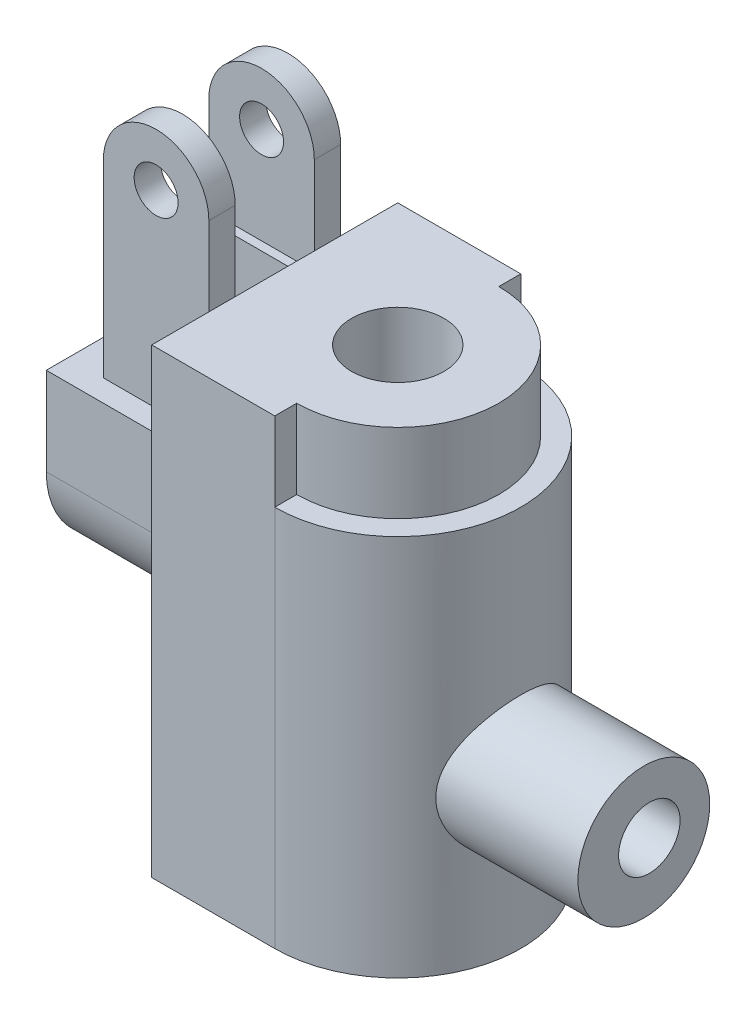
SolidWorks part; units mm, degrees
ref_plane "前视基准面" through (0, 0, 0) normal (0, 0, 1) x (1, 0, 0)
ref_plane "上视基准面" through (0, 0, 0) normal (0, 1, 0) x (1, 0, 0)
ref_plane "右视基准面" through (0, 0, 0) normal (1, 0, 0) x (0, 0, -1)
sketch "草图1" plane through (0, 0, 0) normal (0, 1, 0) x (1, 0, 0)
  line L1 (-14, 28) -> (14, 28)
  line L2 (-14, 28) -> (-14, -28)
  line L3 (-14, -28) -> (14, -28)
  line L5 (-14, 28) -> (14, -28) construction
  line L6 (-14, -28) -> (14, 28) construction
  arc A1 (14, -28) -> (14, 28) centre (14, 0) ccw
  point P0 (0, 0)
  dimension "D3" = 28
  dimension "D1" = 56
  dimension "D2" = 28
extrude "凸台-拉伸1" add sketch "草图1" along normal blind 105
sketch "草图2" plane through (-14, 0, 0) normal (-1, 0, 0) x (0, 0, 1)
  line L0 (0, 70) -> (0, 0) construction
  line L1 (-20, 80) -> (20, 80)
  line L2 (-20, 80) -> (-20, 60)
  line L3 (-20, 60) -> (20, 60)
  line L4 (20, 80) -> (20, 60)
  line L5 (-20, 80) -> (20, 60) construction
  line L6 (-20, 60) -> (20, 80) construction
  arc A0 (20, 60) -> (-20, 60) centre (0, 60) cw
  point P0 (0, 70)
  dimension "D3" = 70
  dimension "D1" = 20
  dimension "D2" = 40
extrude "凸台-拉伸2" add sketch "草图2" along normal blind 32 contours A0 L3 | L4 L1 L2 L3 region at (-14, 70, 0) region at (-14, 51.5117, 0)
ref_plane "基准面1" through (42, 0, 0) normal (1, 0, 0) x (0, 0, -1)
sketch "草图3" plane through (42, 0, 0) normal (1, 0, 0) x (0, 0, -1)
  line L0 (-28, 0) -> (28, 0) construction
  line L1 (0, 35) -> (0, -0.708) construction
  circle A0 centre (0, 35) radius 15
  dimension "D1" = 30
  dimension "D2" = 35
extrude "凸台-拉伸4" add sketch "草图3" against normal up to surface (4.3568 mm away) contours A0 up to face at (28, 52.5, 0)
sketch "草图4" plane through (42, 0, 0) normal (1, 0, 0) x (0, 0, -1)
  arc A2 (0, 50) -> (0, 20) centre (0, 35) ccw
  arc A3 (0, 20) -> (0, 50) centre (0, 35) ccw
  arc A4 (0, 50) -> (0, 20) centre (0, 35) ccw
  arc A5 (0, 20) -> (0, 50) centre (0, 35) ccw
  dimension "D1" = 0
extrude "凸台-拉伸5" add sketch "草图4" along normal offset from surface (28 mm away) 116 up to face at (-46, 65, 0)
sketch "草图5" plane through (0, 0, 0) normal (0, 0, 1) x (1, 0, 0)
  line L0 (-14, 0) -> (14, 0) construction
  line L1 (-38, 123) -> (-14, 123)
  line L2 (-38, 123) -> (-38, 80)
  line L3 (-38, 80) -> (-14, 80)
  line L4 (-14, 123) -> (-14, 80)
  line L5 (-38, 123) -> (-14, 80) construction
  line L6 (-38, 80) -> (-14, 123) construction
  arc A0 (-14, 123) -> (-38, 123) centre (-26, 123) ccw
  point P0 (-26, 101.5)
  dimension "D1" = 24
  dimension "D2" = 123
extrude "凸台-拉伸6" add sketch "草图5" along normal blind 8 from offset 7 contours L4 L1 L2 L3 | L1 A0 region at (-26, 128.093, 0) region at (-26, 101.5, 0)
mirror "镜向1" about plane through (0, 0, 0) normal (0, 0, 1) of "凸台-拉伸6"
sketch "草图6" plane through (0, 0, 0) normal (0, 0, 1) x (1, 0, 0)
  line L0 (-26, 126) -> (-26, 80) construction
  line L1 (-38, 151) -> (-14, 151)
  line L2 (-38, 151) -> (-38, 101)
  line L3 (-38, 101) -> (-14, 101)
  line L4 (-14, 151) -> (-14, 101)
  line L5 (-38, 151) -> (-14, 101) construction
  line L6 (-38, 101) -> (-14, 151) construction
  line L7 (-38, 80) -> (-14, 80) construction
  line L8 (-46, 80) -> (-14, 80) construction
  line L9 (-38, 123) -> (-38, 80) construction
  point P0 (-26, 126)
  point P11 (-9.3633, 126)
  dimension "D1" = 50
  dimension "D2" = 21
extrude "切除-拉伸1" cut sketch "草图6" against normal mid plane 18
sketch "草图7" plane through (0, 0, 15) normal (0, 0, 1) x (1, 0, 0)
  circle A0 centre (-26, 123) radius 5
  arc A1 (-14, 123) -> (-38, 123) centre (-26, 123) ccw construction
  dimension "D1" = 10
extrude "切除-拉伸2" cut sketch "草图7" against normal through all both and the other way through all
sketch "草图8" plane through (0, 0, 0) normal (0, 0, 1) x (1, 0, 0)
  line L0 (-14, 5) -> (-43.3685, 40)
  line L1 (-14, 105) -> (-14, 0) construction
  line L2 (-46, 40) -> (-14, 40) construction
  point P6 (-43.9738, 40)
  dimension "D1" = 35
  dimension "D2" = 40
rib "筋1" sketch "草图8" sketch "草图8" thickness 6 extrusion direction parallel to sketch draft on no parameters "D1"=6
sketch "草图9" plane through (0, 105, 0) normal (0, 1, 0) x (1, 0, 0)
  line L0 (14, 23) -> (14, 28)
  line L1 (14, -23) -> (14, -28)
  line L2 (14, -23) -> (14, 23) construction
  line L12 (14, 28) -> (-14, 28)
  line L13 (-14, 28) -> (-14, 15)
  line L14 (-14, 15) -> (-14, 9)
  line L16 (-14, 9) -> (-14, -9)
  line L18 (-14, -9) -> (-14, -15)
  line L19 (-14, -15) -> (-14, -28)
  line L20 (-14, -28) -> (14, -28)
  line L21 (14, 28) -> (-14, 28)
  line L22 (-14, 28) -> (-14, 15)
  line L23 (-14, 15) -> (-14, 9)
  line L25 (-14, 9) -> (-14, -9)
  line L27 (-14, -9) -> (-14, -15)
  line L28 (-14, -15) -> (-14, -28)
  line L29 (-14, -28) -> (14, -28)
  arc A0 (14, 23) -> (14, -23) centre (14, 0) cw
  arc A1 (14, -28) -> (14, 28) centre (14, 0) ccw construction
  arc A3 (14, -28) -> (14, 28) centre (14, 0) ccw
  arc A4 (14, -28) -> (14, 28) centre (14, 0) ccw
  point P7 (10.5863, 22.7453)
  arc M13 (14, -28) -> (14, 28) centre (14, 0) ccw
  dimension "D1" = 23
  dimension "D2" = 0
extrude "切除-拉伸3" cut sketch "草图9" against normal blind 18 contours L0 A0 L1 M13 region at (14.6261, 105, -25.5)
hole_wizard "M36 螺纹孔2" positions "3D草图2" profile "草图12" tap size "M36" standard "GB"
sketch3d "3D草图2"
  arc A0 (14, 0, 28) -> (14, 0, -28) centre (14, 0, 0) ccw construction
  point P0 (14, 0, 0)
  point P6 (14, 28, 0)
sketch "草图12" plane through (14, 0, 0) normal (1, 0, 0) x (0, 0, -1)
  line L0 (0, 0) -> (0, 64.6138)
  line L1 (0, 64.6138) -> (16, 55)
  line L2 (16, 55) -> (16, 0)
  line L5 (16, 0) -> (0, 0)
  line L10 (0, 64.6138) -> (-16, 55) construction
  line L11 (0, -6.35) -> (0, 107.95) construction
  dimension "螺纹孔钻头直径" = 32
  dimension "螺纹孔钻头深度" = 55
  dimension "导头角度" = 118
cosmetic thread "孔螺蚊线2" parameters "D1"=6, "D2"=36
sketch "草图14" plane through (0, 0, 0) normal (0, -1, 0) x (1, 0, 0)
  circle A0 centre (14, 0) radius 11.5
  dimension "D1" = 23
extrude "切除-拉伸4" cut sketch "草图14" against normal blind 78
hole_wizard "M24 螺纹孔1" positions "3D草图3" profile "草图15" tap size "M24" standard "GB"
sketch3d "3D草图3"
  arc A0 (14, 105, -23) -> (14, 105, 23) centre (14, 105, 0) ccw construction
  point P0 (14, 105, 0)
  point P6 (14, 82, 0)
sketch "草图15" plane through (14, 105, 0) normal (1, 0, 0) x (0, 0, 1)
  line L0 (0, 0) -> (0, 22.309)
  line L1 (0, 22.309) -> (10.5, 16)
  line L2 (10.5, 16) -> (10.5, 0)
  line L5 (10.5, 0) -> (0, 0)
  line L10 (0, 22.309) -> (-10.5, 16) construction
  line L11 (0, -6.35) -> (0, 107.95) construction
  dimension "螺纹孔钻头直径" = 21
  dimension "螺纹孔钻头深度" = 16
  dimension "导头角度" = 118
cosmetic thread "孔螺蚊线3" parameters "D1"=12, "D2"=24
sketch "草图16" plane through (0, 105, 0) normal (0, 1, 0) x (1, 0, 0)
  circle A0 centre (14, 0) radius 5
  dimension "D1" = 10
extrude "切除-拉伸5" cut sketch "草图16" against normal through all both and the other way through all
hole_wizard "M16 螺纹孔1" positions "3D草图5" profile "草图19" tap size "M16" standard "GB" end condition up to next
sketch3d "3D草图5"
  line L0 (-14, 0, -28) -> (-14, 0, 28) construction
  point P0 (-46, 68.9348, -0.0636)
  dimension "D1" = 76
sketch "草图19" plane through (-46, 68.9348, -0.0636) normal (0, 1, 0) x (0, 0, 1)
  line L0 (0, 0) -> (0, 48.5002)
  line L1 (0, 48.5002) -> (7, 48.5002)
  line L2 (7, 48.5002) -> (7, 0)
  line L5 (7, 0) -> (0, 0)
  line L11 (0, -6.35) -> (0, 107.95) construction
  dimension "通孔螺纹孔钻头直径" = 14
  dimension "通孔螺纹孔钻头深度" = 48.5002
cosmetic thread "孔螺蚊线5" parameters "D1"=20, "D2"=16
hole_wizard "M16 螺纹孔2" positions "3D草图6" profile "草图20" tap size "M16" standard "GB" end condition up to next
sketch3d "3D草图6"
  point P0 (70, 35.1892, -1.2575)
  point P2 (918.0269, 244.9231, 0)
sketch "草图20" plane through (70, 35.1892, -1.2575) normal (0, 1, 0) x (0, 0, -1)
  line L0 (0, 0) -> (0, 40.0495)
  line L1 (0, 40.0495) -> (7, 40.0495)
  line L2 (7, 40.0495) -> (7, 0)
  line L5 (7, 0) -> (0, 0)
  line L11 (0, -6.35) -> (0, 107.95) construction
  dimension "通孔螺纹孔钻头直径" = 14
  dimension "通孔螺纹孔钻头深度" = 40.0495
cosmetic thread "孔螺蚊线6" parameters "D1"=20, "D2"=16
cosmetic thread "孔螺蚊线7" parameters "D1"=20, "D2"=16
